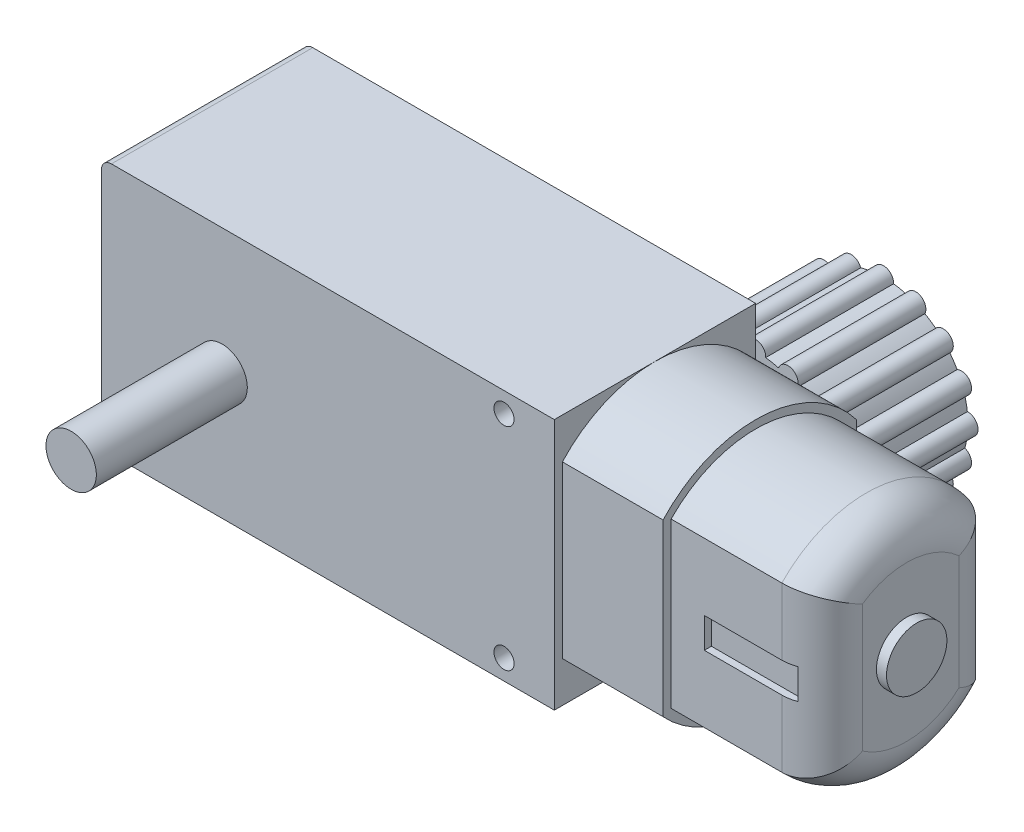
SolidWorks part; units mm, degrees
ref_plane "Front Plane" through (0, 0, 0) normal (0, 0, 1) x (1, 0, 0)
ref_plane "Top Plane" through (0, 0, 0) normal (0, 1, 0) x (1, 0, 0)
ref_plane "Right Plane" through (0, 0, 0) normal (1, 0, 0) x (0, 0, -1)
sketch "Sketch1" plane through (0, 0, 0) normal (0, 0, 1) x (1, 0, 0)
  line L1 (35, -12.5) -> (-35, -12.5)
  line L2 (35, -12.5) -> (35, 12.5)
  line L3 (35, 12.5) -> (-35, 12.5)
  line L4 (-35, -12.5) -> (-35, 12.5)
  line L5 (35, -12.5) -> (-35, 12.5) construction
  line L6 (35, 12.5) -> (-35, -12.5) construction
  point P0 (0, 0)
  dimension "D1" = 70
  dimension "D2" = 25
extrude "Boss-Extrude1" add sketch "Sketch1" along normal mid plane 20
sketch "Sketch2" plane through (35, 0, 0) normal (1, 0, 0) x (0, 0, -1)
  line L1 (-10, -7.5) -> (-10, -12.5)
  line L2 (10, 7.5) -> (10, 12.5)
  line L5 (10, -12.5) -> (10, 12.5)
  line L6 (10, 12.5) -> (-10, 12.5)
  line L7 (-10, 12.5) -> (-10, -12.5)
  line L8 (-10, -12.5) -> (10, -12.5)
  line L9 (10, -12.5) -> (10, -7.5)
  line L10 (10, 12.5) -> (-10, 12.5)
  line L11 (-10, 12.5) -> (-10, 7.5)
  line L12 (-10, -12.5) -> (10, -12.5)
  arc A0 (-10, -7.5) -> (10, -7.5) centre (0, 0) ccw
  arc A1 (10, 7.5) -> (-10, 7.5) centre (0, 0) ccw
  line M6 (10, -12.5) -> (10, 12.5)
  line M7 (10, 12.5) -> (-10, 12.5)
  line M8 (-10, 12.5) -> (-10, -12.5)
  line M9 (-10, -12.5) -> (10, -12.5)
  dimension "D1" = 0
extrude "Cut-Extrude2" cut sketch "Sketch2" against normal blind 25 contours A1 L10 M8 | A1 M6 M7 | A0 L12 M6 | A0 M8 M9 region at (35, -11.0705, 7.611) region at (35, 11.0705, 7.611) region at (35, -11.0705, -7.611) region at (35, 11.0705, -7.611)
sketch "Sketch4" plane through (35, 0, 0) normal (1, 0, 0) x (0, 0, -1)
  line L0 (-9.2, 8.4623) -> (-9.2, -8.4623)
  line L1 (-10, -7.5) -> (-10, 7.5) construction
  line L2 (-9.2, 8.4623) -> (-11.6207, 8.4623)
  line L3 (-11.6207, 8.4623) -> (-11.6207, -8.4623)
  line L4 (-11.6207, -8.4623) -> (-9.2, -8.4623)
  arc A0 (10, 7.5) -> (-10, 7.5) centre (0, 0) ccw construction
  arc A1 (-10, -7.5) -> (10, -7.5) centre (0, 0) ccw construction
  dimension "D1" = 0.8
extrude "Cut-Extrude3" cut sketch "Sketch4" against normal blind 25
sketch "Sketch5" plane through (35, 0, 0) normal (1, 0, 0) x (0, 0, -1)
  line L2 (-8.4, 8.1443) -> (-8.4, -8.1443)
  line L3 (9.2, -7.2284) -> (9.2, 7.2284)
  line L4 (-9.2, 8.4623) -> (-9.2, -8.4623)
  line L5 (10, -7.5) -> (10, 7.5)
  line L6 (-9.2, 8.4623) -> (-9.2, -8.4623)
  line L7 (10, -7.5) -> (10, 7.5)
  arc A2 (9.2, 7.2284) -> (-8.4, 8.1443) centre (0, 0) ccw
  arc A3 (-8.4, -8.1443) -> (9.2, -7.2284) centre (0, 0) ccw
  arc A4 (10, 7.5) -> (-9.2, 8.4623) centre (0, 0) ccw
  arc A5 (-9.2, -8.4623) -> (10, -7.5) centre (0, 0) ccw
  arc A6 (10, 7.5) -> (-9.2, 8.4623) centre (0, 0) ccw
  arc A7 (-9.2, -8.4623) -> (10, -7.5) centre (0, 0) ccw
  dimension "D1" = 0
  dimension "D2" = 0.8
extrude "Cut-Extrude4" cut sketch "Sketch5" against normal blind 15
fillet "Fillet1" radius 4 4 edges at (35, 0, -9.2) (35, -11.6842, -0.608) (35, 0, 8.4) (35, 11.6842, -0.608)
sketch "Sketch6" plane through (35, 0, 0) normal (1, 0, 0) x (0, 0, -1)
  circle A0 centre (0, 0) radius 3
  dimension "D1" = 6
extrude "Boss-Extrude2" add sketch "Sketch6" along normal blind 1
sketch "Sketch7" plane through (0, 0, -9.2) normal (0, 0, -1) x (-1, 0, 0)
  line L0 (-31, 7.2284) -> (-31, -7.2284) construction
  line L1 (-32.3651, -1.5) -> (-23.3004, -1.5)
  line L2 (-32.3651, -1.5) -> (-32.3651, 1.5)
  line L3 (-32.3651, 1.5) -> (-23.3004, 1.5)
  line L4 (-23.3004, -1.5) -> (-23.3004, 1.5)
  point P6 (-31, 0)
  point P7 (-23.3004, 0)
  dimension "D1" = 3
extrude "Cut-Extrude5" cut sketch "Sketch7" against normal blind 1.5
mirror "Mirror1" about plane through (0, 0, 0) normal (0, 0, 1) of "Cut-Extrude5"
fillet "Fillet2" radius 1 2 edges at (-35, 12.5, 0) (-35, -12.5, 0)
sketch "Sketch8" plane through (0, 0, 0) normal (0, 0, 1) x (1, 0, 0)
  line L0 (-35, 11.5) -> (-35, -11.5) construction
  line L1 (-35, -2.5) -> (-40, -2.5)
  line L2 (-35, -2.5) -> (-35, 2.5)
  line L3 (-35, 2.5) -> (-40, 2.5)
  line L4 (-40, -2.5) -> (-40, 2.5)
  circle A0 centre (-37.5, 0) radius 1.5
  point P6 (-40, 0)
  dimension "D3" = 3
  dimension "D1" = 5
  dimension "D2" = 5
extrude "Boss-Extrude3" add sketch "Sketch8" along normal mid plane 3.5
sketch "Sketch9" plane through (0, 0, 10) normal (0, 0, 1) x (1, 0, 0)
  line L0 (8.2693, 0) -> (-21.3687, 0) construction
  line L1 (-34, -12.5) -> (10, -12.5) construction
  line L2 (-35, 11.5) -> (-35, -11.5) construction
  circle A0 centre (5, -10.5) radius 1
  circle A1 centre (5, 10.5) radius 1
  dimension "D1" = 2
  dimension "D2" = 2
  dimension "D3" = 40
extrude "Cut-Extrude7" cut sketch "Sketch9" along normal through all and the other way through all
sketch "Sketch10" plane through (0, 0, -10) normal (0, 0, -1) x (-1, 0, 0)
  line L0 (35, 11.5) -> (35, -11.5) construction
  circle A0 centre (23, 0) radius 2.5
  dimension "D2" = 5
  dimension "D1" = 12
extrude "Cut-Extrude8" cut sketch "Sketch10" against normal through all
sketch "Sketch11" plane through (0, 0, -10) normal (0, 0, -1) x (-1, 0, 0)
  line L0 (0, 0) -> (-20, 0) construction
  line L1 (-20, -7.5) -> (-20, 7.5) construction
  circle A1 centre (-10, 0) radius 8.39
  point P5 (-10, -1.621)
  point P6 (-10, 0)
  dimension "D1" = 16.78
extrude "Boss-Extrude5" add sketch "Sketch11" along normal blind 12.7
sketch "Sketch13" plane through (0, 0, -22.7) normal (0, 0, -1) x (-1, 0, 0)
  line L0 (-10, 0) -> (-10, 8.39) construction
  circle A0 centre (-10, 0) radius 9.39 construction
  circle A1 centre (-10, 0) radius 8.39
  arc A2 (-9.0018, 8.3304) -> (-10.9982, 8.3304) centre (-10, 0) ccw
  arc A3 (-10.9982, 8.3304) -> (-9.0018, 8.3304) centre (-10, 8.39) cw
  circle A4 centre (-10, 0) radius 8.39 construction
  arc A5 (-5.8899, 7.3143) -> (-7.7343, 8.0783) centre (-10, 0) ccw
  arc A6 (-7.7343, 8.0783) -> (-5.8899, 7.3143) centre (-6.7893, 7.7513) cw
  arc A7 (-3.4037, 5.1846) -> (-4.8154, 6.5963) centre (-10, 0) ccw
  arc A8 (-4.8154, 6.5963) -> (-3.4037, 5.1846) centre (-4.0674, 5.9326) cw
  arc A9 (-1.9217, 2.2657) -> (-2.6857, 4.1101) centre (-10, 0) ccw
  arc A10 (-2.6857, 4.1101) -> (-1.9217, 2.2657) centre (-2.2487, 3.2107) cw
  arc A11 (-1.6696, -0.9982) -> (-1.6696, 0.9982) centre (-10, 0) ccw
  arc A12 (-1.6696, 0.9982) -> (-1.6696, -0.9982) centre (-1.61, 0) cw
  arc A13 (-2.6857, -4.1101) -> (-1.9217, -2.2657) centre (-10, 0) ccw
  arc A14 (-1.9217, -2.2657) -> (-2.6857, -4.1101) centre (-2.2487, -3.2107) cw
  arc A15 (-4.8154, -6.5963) -> (-3.4037, -5.1846) centre (-10, 0) ccw
  arc A16 (-3.4037, -5.1846) -> (-4.8154, -6.5963) centre (-4.0674, -5.9326) cw
  arc A17 (-7.7343, -8.0783) -> (-5.8899, -7.3143) centre (-10, 0) ccw
  arc A18 (-5.8899, -7.3143) -> (-7.7343, -8.0783) centre (-6.7893, -7.7513) cw
  arc A19 (-10.9982, -8.3304) -> (-9.0018, -8.3304) centre (-10, 0) ccw
  arc A20 (-9.0018, -8.3304) -> (-10.9982, -8.3304) centre (-10, -8.39) cw
  arc A21 (-14.1101, -7.3143) -> (-12.2657, -8.0783) centre (-10, 0) ccw
  arc A22 (-12.2657, -8.0783) -> (-14.1101, -7.3143) centre (-13.2107, -7.7513) cw
  arc A23 (-16.5963, -5.1846) -> (-15.1846, -6.5963) centre (-10, 0) ccw
  arc A24 (-15.1846, -6.5963) -> (-16.5963, -5.1846) centre (-15.9326, -5.9326) cw
  arc A25 (-18.0783, -2.2657) -> (-17.3143, -4.1101) centre (-10, 0) ccw
  arc A26 (-17.3143, -4.1101) -> (-18.0783, -2.2657) centre (-17.7513, -3.2107) cw
  arc A27 (-18.3304, 0.9982) -> (-18.3304, -0.9982) centre (-10, 0) ccw
  arc A28 (-18.3304, -0.9982) -> (-18.3304, 0.9982) centre (-18.39, 0) cw
  arc A29 (-17.3143, 4.1101) -> (-18.0783, 2.2657) centre (-10, 0) ccw
  arc A30 (-18.0783, 2.2657) -> (-17.3143, 4.1101) centre (-17.7513, 3.2107) cw
  arc A31 (-15.1846, 6.5963) -> (-16.5963, 5.1846) centre (-10, 0) ccw
  arc A32 (-16.5963, 5.1846) -> (-15.1846, 6.5963) centre (-15.9326, 5.9326) cw
  arc A33 (-12.2657, 8.0783) -> (-14.1101, 7.3143) centre (-10, 0) ccw
  arc A34 (-14.1101, 7.3143) -> (-12.2657, 8.0783) centre (-13.2107, 7.7513) cw
  point P60 (-10, 0)
  dimension "D1" = 0
  dimension "D2" = 1
  dimension "D3" = 16
extrude "Boss-Extrude6" add sketch "Sketch13" against normal up to surface (12.7 mm away) up to face at (-13.3505, 0, -10)
sketch "Sketch14" plane through (0, 0, -10) normal (0, 0, -1) x (-1, 0, 0)
  circle A0 centre (23, 0) radius 2.5 construction
  circle A1 centre (23, 0) radius 2.5
extrude "Boss-Extrude7" add sketch "Sketch14" against normal blind 35
